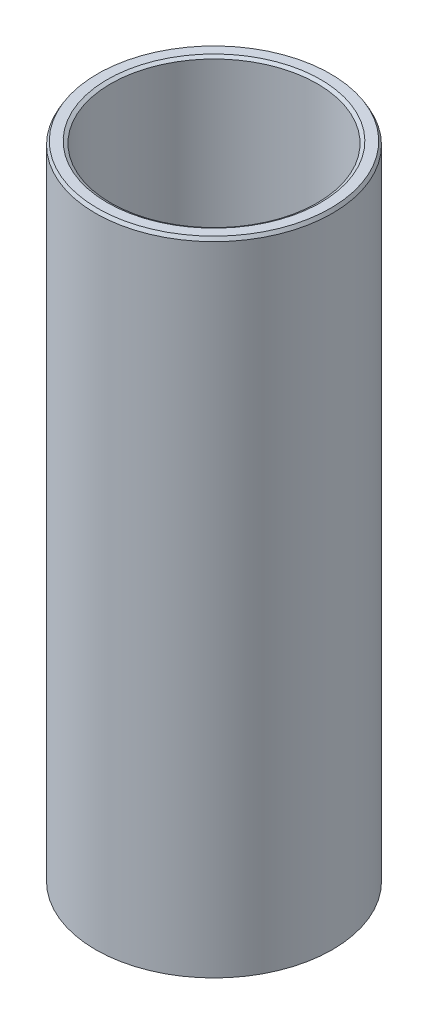
SolidWorks part; units mm, degrees
ref_plane "Front Plane" through (0, 0, 0) normal (0, 0, 1) x (1, 0, 0)
ref_plane "Top Plane" through (0, 0, 0) normal (0, 1, 0) x (1, 0, 0)
ref_plane "Right Plane" through (0, 0, 0) normal (1, 0, 0) x (0, 0, -1)
sketch "Sketch1" plane through (0, 0, 0) normal (0, 1, 0) x (1, 0, 0)
  circle A0 centre (0, 0) radius 47.5
  dimension "SLEEVE_OD" = 95
extrude "Boss-Extrude1" add sketch "Sketch1" along normal blind 257.853
sketch "Sketch2" plane through (0, 0, 0) normal (0, 1, 0) x (1, 0, 0)
  circle A0 centre (0, 0) radius 41.4251
  dimension "BORE_D" = 82.8502
extrude "Cut-Extrude1" cut sketch "Sketch2" along normal through all
chamfer "Chamfer1" distance 1.3556 angle 30 4 edges at (0, 257.853, 41.4251) (0, 0, 41.4251) (0, 0, 47.5) (0, 257.853, 47.5) first distance on face at (0, 257.853, 41.4251) first distance on face at (0, 0, 41.4251) first distance on face at (0, 257.853, 47.5)
